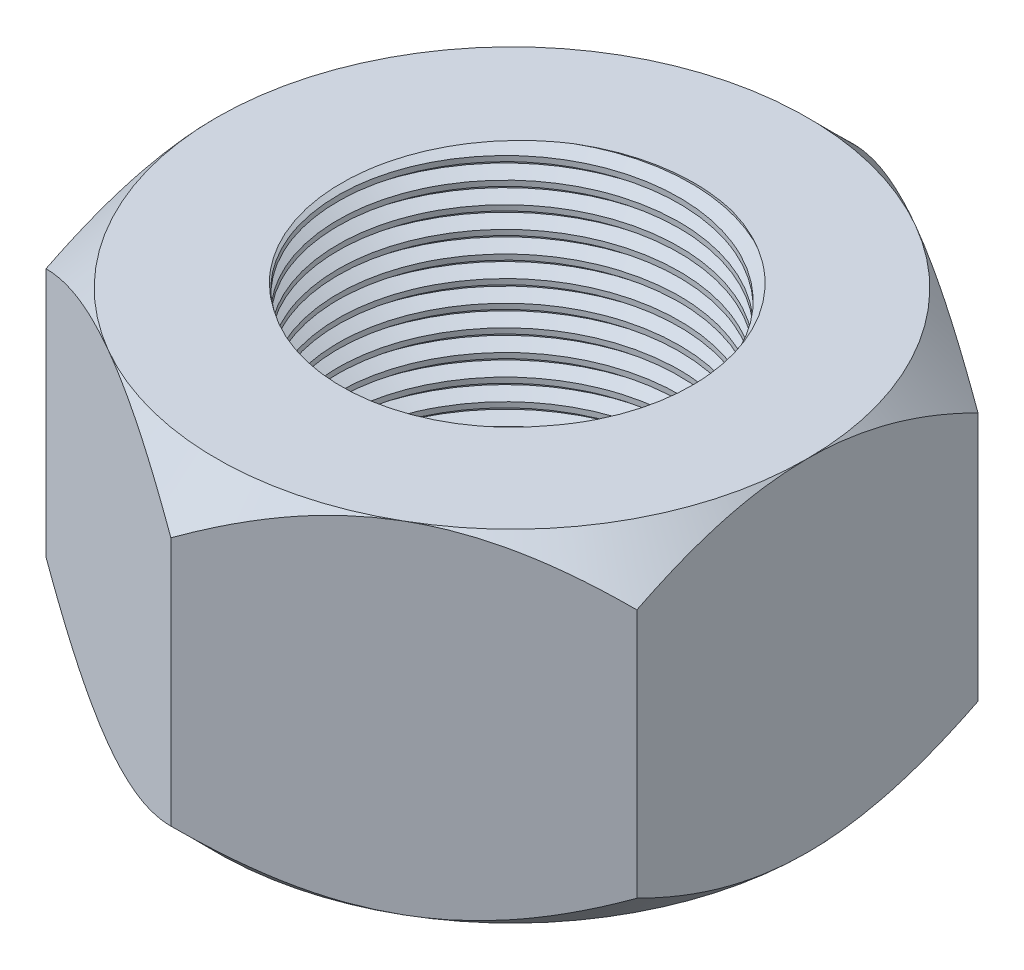
SolidWorks part; units mm, degrees
ref_plane "Front Plane" through (0, 0, 0) normal (0, 0, 1) x (1, 0, 0)
ref_plane "Top Plane" through (0, 0, 0) normal (0, 1, 0) x (1, 0, 0)
ref_plane "Right Plane" through (0, 0, 0) normal (1, 0, 0) x (0, 0, -1)
sketch "Sketch1" plane through (0, 0, 0) normal (0, 1, 0) x (1, 0, 0)
  line L1 (17.3205, -10) -> (17.3205, 10)
  line L2 (17.3205, 10) -> (0, 20)
  line L3 (0, 20) -> (-17.3205, 10)
  line L4 (-17.3205, 10) -> (-17.3205, -10)
  line L5 (-17.3205, -10) -> (0, -20)
  line L6 (0, -20) -> (17.3205, -10)
  circle A0 centre (0, 0) radius 17.3205 construction
  dimension "D1" = 20
extrude "Boss-Extrude1" add sketch "Sketch1" along normal mid plane 20
sketch "Sketch3" plane through (0, -10, 0) normal (0, -1, 0) x (1, 0, 0)
  line L0 (-17.3205, 10) -> (0, 20) construction
  circle A1 centre (0, 0) radius 17.3205
extrude "Cut-Extrude2" cut sketch "Sketch3" against normal blind 10 draft 45 flip side to cut
mirror "Mirror1" about plane through (0, 0, 0) normal (0, 1, 0) of "Cut-Extrude2"
sketch "Sketch4" plane through (0, 10, 0) normal (0, 1, 0) x (1, 0, 0)
  circle A0 centre (0, 0) radius 10
  dimension "D1" = 20
extrude "Cut-Extrude3" cut sketch "Sketch4" against normal up to next
thread "Thread1" pitch 1.25 method cut profile "Thread Profile1" start angle 0, offset 2, length 24, pitch 1.25, diameter 20
ref_plane "Plane1" through (-10, 12, 0) normal (0, 0, 1) x (-1, 0, 0)
sketch "Thread Profile1" plane through (-10, 12, 0) normal (0, 0, 1) x (-1, 0, 0)
  line L0 (0, 0) -> (0, 1.25) construction
  line L1 (0, 0) -> (0.6766, 0.3906)
  line L2 (0.6766, 0.3906) -> (0.6766, 0.5469)
  line L3 (0.6766, 0.5469) -> (0, 0.9375)
  line L4 (0.6766, 0.4687) -> (0, 0.4687) construction
  line L11 (0, 0) -> (0, 0.9375)
  point P2 (0, 0)
  dimension "Pitch" = 1.25
  dimension "Profile_Angle" = 60
  dimension "Profile_Land" = 0.1562
  dimension "Profile_Height" = 0.6766
